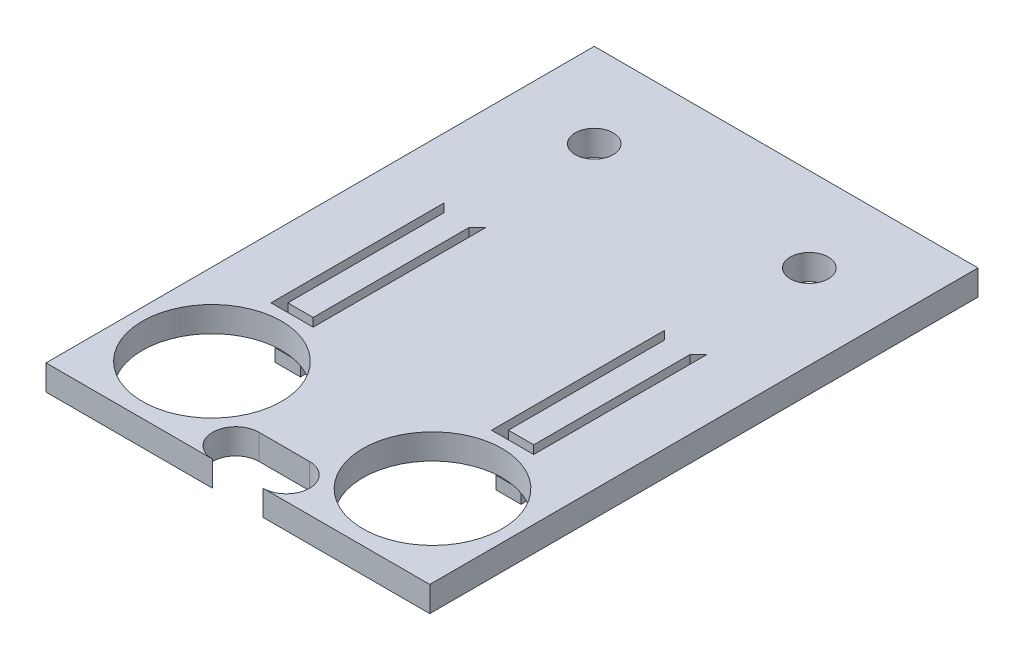
SolidWorks part; units mm, degrees
ref_plane "Front" through (0, 0, 0) normal (0, 0, 1) x (1, 0, 0)
ref_plane "Top" through (0, 0, 0) normal (0, 1, 0) x (1, 0, 0)
ref_plane "Right" through (0, 0, 0) normal (1, 0, 0) x (0, 0, -1)
sketch "Sketch1" plane through (0, 0, 0) normal (0, 0, 1) x (1, 0, 0)
  line L1 (-36.5996, 16.0347) -> (8.9004, 16.0347)
  line L2 (-36.5996, 16.0347) -> (-36.5996, 13.0347)
  line L3 (-36.5996, 13.0347) -> (8.9004, 13.0347)
  line L4 (8.9004, 16.0347) -> (8.9004, 13.0347)
  point P12 (-13.8496, 16.0347)
  dimension "D1" = 45.5
  dimension "D2" = 3
extrude "Boss-Extrude1" add sketch "Sketch1" along normal blind 20 contours L2 L3 L1 | L3 L4 L1 region at (-13.8496, 14.5347, 0)
sketch "Sketch2" plane through (0, 0, 20) normal (0, 0, 1) x (1, 0, 0)
  line L1 (-36.5996, 16.0347) -> (8.9004, 16.0347)
  line L2 (-36.5996, 16.0347) -> (-36.5996, 13.0347)
  line L3 (-36.5996, 13.0347) -> (8.9004, 13.0347)
  line L4 (8.9004, 16.0347) -> (8.9004, 13.0347)
  line L5 (8.9004, 16.0347) -> (8.9004, 13.0347) construction
  dimension "D1" = 3
extrude "Boss-Extrude2" add sketch "Sketch2" along normal blind 45 contours L3 L4 L1 L2
sketch "Sketch3" plane through (0, 13.0347, 0) normal (0, -1, 0) x (-1, 0, 0)
  line L0 (36.5996, -65) -> (-8.9004, -65) construction
  line L1 (18.6746, -55) -> (9.0246, -55)
  circle A0 centre (26.9246, -55) radius 8.25
  circle A1 centre (0.7746, -55) radius 8.25
  point P8 (13.8496, -55)
  point P9 (13.8496, -65)
  dimension "D1" = 16.5
  dimension "D2" = 16.5
  dimension "D3" = 10
  dimension "D4" = 10
  dimension "D5" = 26.15
extrude "Cut-Extrude1" cut sketch "Sketch3" against normal through all contours A0 | A1 region at (-0.7746, 13.0347, 55) region at (-26.9246, 13.0347, 55)
sketch "Sketch5" plane through (0, 13.0347, 0) normal (0, -1, 0) x (-1, 0, 0)
  line L0 (29.4246, -25) -> (29.4246, -45.5)
  line L1 (29.4246, -45.5) -> (24.4246, -45.5)
  line L2 (24.4246, -45.5) -> (24.4246, -25)
  line L3 (24.4246, -25) -> (25.4246, -25)
  line L4 (25.4246, -25) -> (25.4246, -44.5)
  line L5 (25.4246, -44.5) -> (28.4246, -44.5)
  line L6 (28.4246, -44.5) -> (28.4246, -25)
  line L7 (28.4246, -25) -> (29.4246, -25)
  line L8 (36.5996, -65) -> (-8.9004, -65) construction
  line L11 (13.8496, -65) -> (13.8496, -32.1492)
  line L12 (-0.7254, -25) -> (-1.7254, -25)
  line L13 (-0.7254, -44.5) -> (-0.7254, -25)
  line L14 (2.2746, -44.5) -> (-0.7254, -44.5)
  line L15 (2.2746, -25) -> (2.2746, -44.5)
  line L16 (3.2746, -25) -> (2.2746, -25)
  line L17 (3.2746, -45.5) -> (3.2746, -25)
  line L18 (-1.7254, -45.5) -> (3.2746, -45.5)
  line L19 (-1.7254, -25) -> (-1.7254, -45.5)
  point P2 (26.9246, -45.5)
  point P9 (0.7746, -55)
  point P11 (26.9246, -55)
  point P17 (13.8496, -65)
  point P28 (0.7746, -45.5)
  dimension "D1" = 1
  dimension "D2" = 1
  dimension "D3" = 3
  dimension "D4" = 1
  dimension "D5" = 19.5
  dimension "D6" = 40
extrude "Cut-Extrude2" cut sketch "Sketch5" along direction (0, -1, 0) on the side against the normal through all contours L0 L1 L2 L3 L4 L5 L6 L7 | L17 L16 L15 L14 L13 L12 L19 L18
sketch "Sketch6" plane through (-25.4246, 0, 0) normal (1, 0, 0) x (0, 0, -1)
  line L0 (-65, 13.0347) -> (0, 13.0347) construction
  line L1 (-44.5, 13.0347) -> (-46, 12.1687)
  line L2 (-46, 12.1687) -> (-46, 10.6687)
  line L3 (-46, 10.6687) -> (-41.5, 10.6687)
  line L4 (-41.5, 10.6687) -> (-39.134, 13.0347)
  line L5 (-25, 13.0347) -> (-44.5, 13.0347) construction
  line L6 (-39.134, 13.0347) -> (-44.5, 13.0347)
  dimension "D1" = 3
  dimension "D2" = 45
  dimension "D3" = 1.5
  dimension "D4" = 60
  dimension "D5" = 1.5
extrude "Boss-Extrude4" add sketch "Sketch6" against normal blind 3
sketch "Sketch8" plane through (0, 13.0347, 0) normal (0, -1, 0) x (-1, 0, 0)
  line L0 (25.4246, -25) -> (2.2746, -25)
  point P4 (13.8496, -25)
  dimension "D1" = 23.15
ref_plane "Plane5" through (-13.8496, 13.0347, 25) normal (1, 0, 0) x (0, 0, -1)
mirror "Mirror7" about plane through (-13.8496, 13.0347, 25) normal (1, 0, 0) of "Boss-Extrude4"
sketch "Sketch9" plane through (0, 13.0347, 0) normal (0, -1, 0) x (-1, 0, 0)
  line L0 (16.8496, -65) -> (10.8496, -65)
  line L1 (16.8496, -59.5) -> (10.8496, -59.5)
  line L2 (36.5996, -65) -> (-8.9004, -65) construction
  arc A0 (16.8496, -65) -> (16.8496, -59.5) centre (16.8496, -62.25) ccw
  arc A1 (10.8496, -65) -> (10.8496, -59.5) centre (10.8496, -62.25) cw
  point P8 (13.8496, -65)
  point P9 (13.8496, -65)
  dimension "D2" = 6
  dimension "D1" = 5.5
extrude "Cut-Extrude3" cut sketch "Sketch9" against normal through all
sketch "Sketch10" plane through (0, 13.0347, 0) normal (0, -1, 0) x (-1, 0, 0)
  line L0 (10.8496, -59.5) -> (16.8496, -59.5) construction
  line L1 (8.8496, -47.5) -> (18.8496, -47.5)
  line L2 (8.8496, -47.5) -> (8.8496, -45)
  line L3 (8.8496, -45) -> (18.8496, -45)
  line L4 (18.8496, -47.5) -> (18.8496, -45)
  line L5 (36.5996, -65) -> (16.8496, -65) construction
  point P4 (13.8496, -47.5)
  point P9 (13.8496, -59.5)
  dimension "D1" = 10
  dimension "D2" = 2.5
  dimension "D3" = 20
extrude "Cut-Extrude4" cut sketch "Sketch10" against normal blind 2 contours L1 L4 L3 L2
sketch "Sketch13" plane through (0, 13.0347, 0) normal (0, -1, 0) x (-1, 0, 0)
  line L1 (28.4246, -39.134) -> (25.4246, -39.134)
  line L2 (28.4246, -39.134) -> (28.4246, -25)
  line L3 (28.4246, -25) -> (25.4246, -25)
  line L4 (25.4246, -39.134) -> (25.4246, -25)
  line L5 (2.2746, -39.134) -> (-0.7254, -39.134)
  line L6 (2.2746, -39.134) -> (2.2746, -25)
  line L7 (2.2746, -25) -> (-0.7254, -25)
  line L8 (-0.7254, -39.134) -> (-0.7254, -25)
extrude "Cut-Extrude6" cut sketch "Sketch13" against normal blind 1
chamfer "Chamfer1" distance 1 angle 45 2 edges at (-26.9246, 14.0347, 25) (-0.7746, 14.0347, 25)
sketch "Sketch15" plane through (0, 16.0347, 0) normal (0, 1, 0) x (1, 0, 0)
  line L0 (-36.5996, 0) -> (8.9004, 0) construction
  line L1 (-36.5996, -65) -> (-36.5996, 0) construction
  line L2 (8.9004, -65) -> (8.9004, 0) construction
  circle A0 centre (-26.5996, -10) radius 2.25
  circle A1 centre (-1.0996, -10) radius 2.25
  dimension "D1" = 10
  dimension "D2" = 10
  dimension "D3" = 4.5
  dimension "D4" = 4.5
  dimension "D5" = 10
  dimension "D6" = 10
extrude "Cut-Extrude7" cut sketch "Sketch15" against normal through all
chamfer "Chamfer2" distance 1 angle 45 4 edges at (-28.4246, 14.5347, 25) (-25.4246, 14.5347, 25) (-2.2746, 14.5347, 25) (0.7254, 14.5347, 25)
